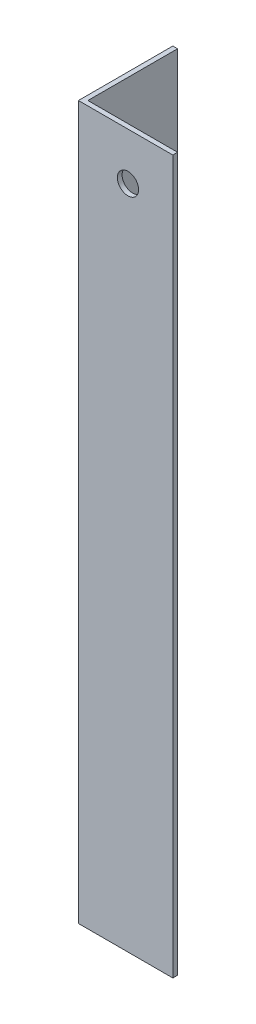
SolidWorks part; units mm, degrees
material "1060 Сплав"
ref_plane "Спереди" through (0, 0, 0) normal (0, 0, 1) x (1, 0, 0)
ref_plane "Сверху" through (0, 0, 0) normal (0, 1, 0) x (1, 0, 0)
ref_plane "Справа" through (0, 0, 0) normal (1, 0, 0) x (0, 0, -1)
sketch "Эскиз1" plane through (0, 0, 0) normal (0, 1, 0) x (1, 0, 0)
  line L0 (0, 0) -> (0, 20)
  line L1 (0, 20) -> (1, 20)
  line L2 (1, 20) -> (1, 1)
  line L3 (1, 1) -> (20, 1)
  line L4 (20, 1) -> (20, 0)
  line L5 (20, 0) -> (0, 0)
  dimension "D1" = 1
  dimension "D2" = 20
extrude "Бобышка-Вытянуть1" add sketch "Эскиз1" along normal blind 151
sketch "Эскиз2" plane through (0, 0, -1) normal (0, 0, -1) x (-1, 0, 0)
  line L0 (-10.5, 151) -> (-10.5, 141) construction
  line L1 (-20, 151) -> (-1, 151) construction
  circle A0 centre (-10.5, 141) radius 2.25
  dimension "D2" = 4.5
  dimension "D1" = 10
extrude "Вырез-Вытянуть1" cut sketch "Эскиз2" against normal through all
sketch "Эскиз3" plane through (1, 0, 0) normal (1, 0, 0) x (0, 0, -1)
  line L0 (10.5, 151) -> (10.5, 0) construction
  line L1 (1, 151) -> (20, 151) construction
  line L2 (1, 0) -> (20, 0) construction
  line L4 (122, 20) -> (-20, 20) construction
  line L5 (122, 126) -> (-20, 126) construction
  line L6 (122, 126) -> (-20, 126) construction
  line L8 (20, 151) -> (0, 151) construction
  line L9 (122, 20) -> (-20, 20) construction
  circle A0 centre (10.5, 116.5) radius 2.25
  circle A1 centre (10.5, 9.5) radius 2.25
  dimension "D1" = 34.5
  dimension "D2" = 4.5
  dimension "D3" = 9.5
  dimension "D4" = 4.5
extrude "Вырез-Вытянуть2" cut sketch "Эскиз3" against normal through all
